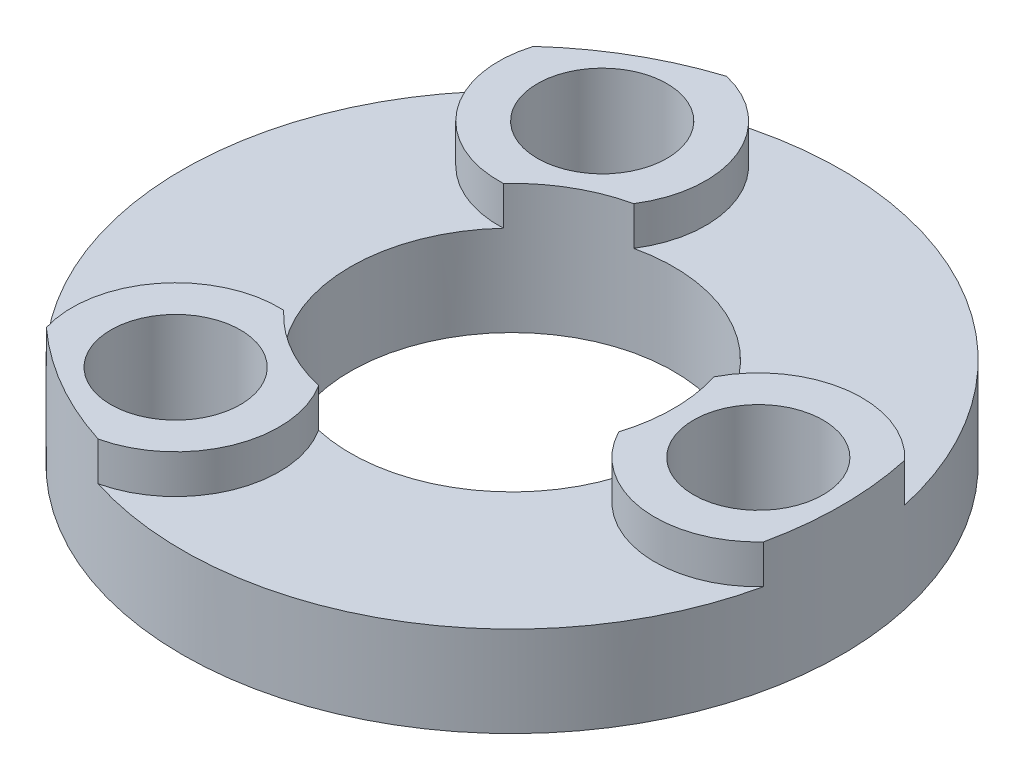
SolidWorks part; units mm, degrees
material "ABS"
ref_plane "Front Plane" through (0, 0, 0) normal (0, 0, 1) x (1, 0, 0)
ref_plane "Top Plane" through (0, 0, 0) normal (0, 1, 0) x (1, 0, 0)
ref_plane "Right Plane" through (0, 0, 0) normal (1, 0, 0) x (0, 0, -1)
sketch "Sketch1" plane through (0, 0, 0) normal (0, 1, 0) x (1, 0, 0)
  circle A2 centre (-9.5263, -16.4999) radius 3.175 construction
  circle A3 centre (-9.5262, 16.4999) radius 3.175 construction
  circle A4 centre (19.0525, 0) radius 3.175 construction
  circle A5 centre (-9.5262, 16.4999) radius 3.175
  circle A6 centre (19.0525, 0) radius 3.175
  circle A7 centre (-9.5263, -16.4999) radius 3.175
  circle A15 centre (0, 0) radius 12.5
  circle A16 centre (0, 0) radius 25.5
  point P1 (30.1365, 0)
  point P12 (-9.5263, -16.4999)
  point P14 (19.0525, 0)
  point P16 (-9.5262, 16.4999)
  point P20 (-4.9245, 20.2425)
  point P29 (-4.9245, -20.2425)
  dimension "D1" = 51
  dimension "D3" = 6.35
  dimension "D4" = 25
  dimension "D2" = 19.0525
extrude "Boss-Extrude1" add sketch "Sketch1" along normal blind 10 contours A7 | A5 | A6 | A5 A6 A7 region at (-9.5262, 0, -16.4999) region at (19.0525, 0, 0) region at (-9.5262, 0, 16.4999) region at (-24.7788, 0, 0)
sketch "Sketch3" plane through (0, 10, 0) normal (0, 1, 0) x (1, 0, 0)
  circle A1 centre (19.0525, 0) radius 5.0125
  dimension "D1" = 10.025
extrude "Cut-Extrude1" cut sketch "Sketch3" against normal blind 7.5
sketch "Sketch5" plane through (0, 0, 0) normal (0, 0, 1) x (1, 0, 0)
  line L0 (0, 0) -> (0, 1.348) construction
pattern_circular "CirPattern1" count 3 every 120 about axis through (0, 0, 0) along (0, 1, 0) of "Cut-Extrude1"
sketch "Sketch6" plane through (0, 10, 0) normal (0, 1, 0) x (1, 0, 0)
  circle A6 centre (-9.5262, 16.4999) radius 8.0125
  arc A7 (-17.1914, 18.8337) -> (-9.1694, 8.4954) centre (-9.5262, 16.4999) ccw
  circle A9 centre (19.0525, 0) radius 8.0125
  arc A10 (11.9419, -3.6932) -> (24.9061, -5.4713) centre (19.0525, 0) ccw
  circle A11 centre (0, 0) radius 12.5 construction
  circle A12 centre (-9.5262, -16.4999) radius 8.0125
  arc A13 (-9.1694, -8.4954) -> (-17.1914, -18.8337) centre (-9.5262, -16.4999) ccw
  circle A14 centre (0, 0) radius 25.5 construction
  arc A15 (-2.7725, -12.1886) -> (11.9419, -3.6932) centre (0, 0) ccw
  arc A16 (-7.7148, -24.305) -> (24.9061, -5.4713) centre (0, 0) ccw
  arc A17 (-2.7725, 12.1886) -> (-7.7148, 24.305) centre (-9.5262, 16.4999) ccw
  arc A18 (24.9061, 5.4713) -> (11.9419, 3.6932) centre (19.0525, 0) ccw
  arc A19 (-7.7148, -24.305) -> (-2.7725, -12.1886) centre (-9.5262, -16.4999) ccw
  arc A20 (24.9061, 5.4713) -> (-7.7148, 24.305) centre (0, 0) ccw
  arc A21 (11.9419, 3.6932) -> (-2.7725, 12.1886) centre (0, 0) ccw
  arc A22 (-9.1694, 8.4954) -> (-9.1694, -8.4954) centre (0, 0) ccw
  arc A23 (-17.1914, 18.8337) -> (-17.1914, -18.8337) centre (0, 0) ccw
  dimension "D1" = 3
  dimension "D2" = 3
  dimension "D3" = 3
extrude "Cut-Extrude2" cut sketch "Sketch6" against normal blind 3
